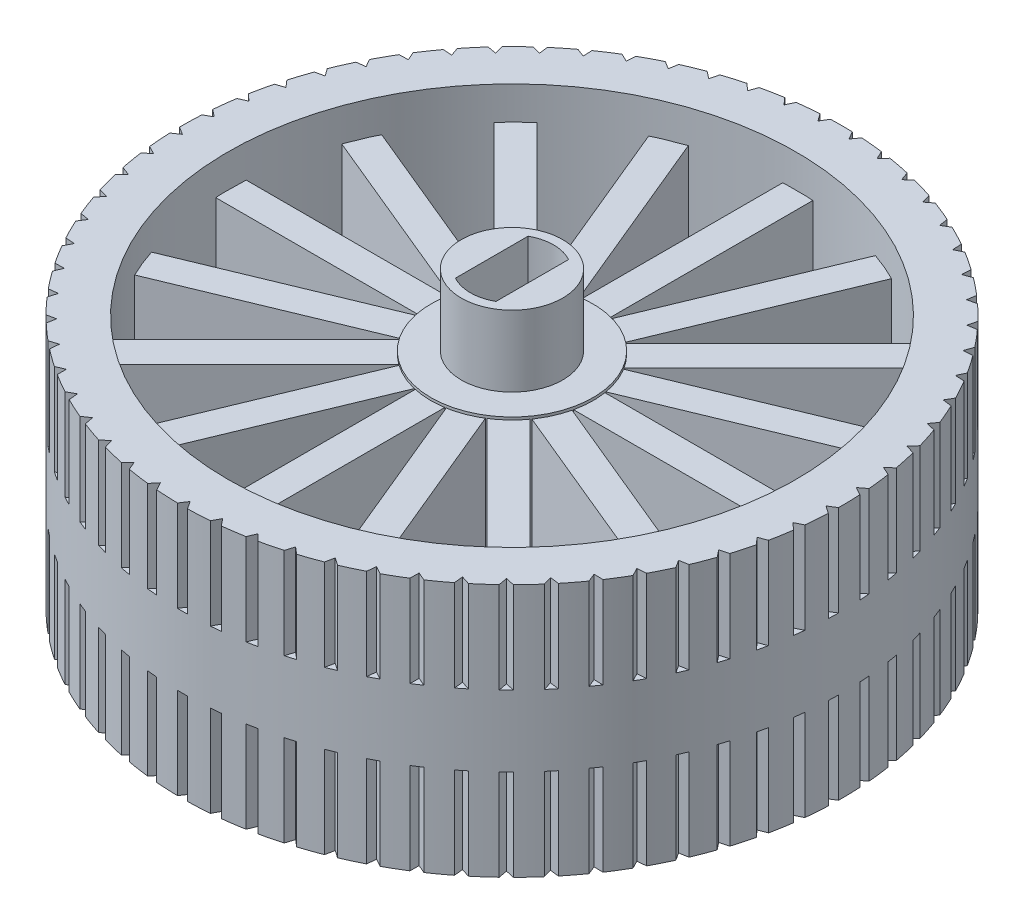
SolidWorks part; units mm, degrees
ref_plane "Front Plane" through (0, 0, 0) normal (0, 0, 1) x (1, 0, 0)
ref_plane "Top Plane" through (0, 0, 0) normal (0, 1, 0) x (1, 0, 0)
ref_plane "Right Plane" through (0, 0, 0) normal (1, 0, 0) x (0, 0, -1)
sketch "Sketch1" plane through (0, 0, 0) normal (0, 1, 0) x (1, 0, 0)
  circle A0 centre (0, 0) radius 32.5
extrude "Boss-Extrude1" add sketch "Sketch1" along normal blind 2
sketch "Sketch2" plane through (0, 2, 0) normal (0, 1, 0) x (1, 0, 0)
  circle A0 centre (0, 0) radius 4
extrude "Boss-Extrude2" add sketch "Sketch2" along normal blind 2
sketch "Sketch4" plane through (0, 4, 0) normal (0, 1, 0) x (1, 0, 0)
  line L0 (0, 4) -> (0, -4) construction
  line L1 (-4, 0) -> (-1.895, 0) construction
  line L4 (1.995, -3.5819) -> (1.995, 3.5819)
  line L5 (-1.995, 3.5819) -> (-1.995, -3.5819)
  line L7 (0, 0) -> (4, 0) construction
  circle A0 centre (0, 0) radius 4 construction
  arc A4 (1.995, 3.5819) -> (-1.995, 3.5819) centre (0, 0) ccw
  arc A5 (-1.995, -3.5819) -> (1.995, -3.5819) centre (0, 0) ccw
  point P7 (0, 0)
  point P11 (0, 0)
  point P16 (1.895, 0)
extrude "Cut-Extrude1" cut sketch "Sketch4" against normal blind 28
sketch "Sketch5" plane through (0, 2, 0) normal (0, 1, 0) x (1, 0, 0)
  circle A0 centre (0, 0) radius 8
extrude "Boss-Extrude3" add sketch "Sketch5" along normal blind 2
sketch "Sketch6" plane through (0, 2, 0) normal (0, -1, 0) x (1, 0, 0)
  line L2 (-1.995, 3.5819) -> (-1.995, -3.5819)
  line L3 (1.995, -3.5819) -> (1.995, 3.5819)
  line L4 (-1.995, 3.5819) -> (-1.995, -3.5819)
  line L5 (1.995, -3.5819) -> (1.995, 3.5819)
  arc A2 (1.995, 3.5819) -> (-1.995, 3.5819) centre (0, 0) ccw
  arc A3 (-1.995, -3.5819) -> (1.995, -3.5819) centre (0, 0) ccw
  arc A4 (1.995, 3.5819) -> (-1.995, 3.5819) centre (0, 0) ccw
  arc A5 (-1.995, -3.5819) -> (1.995, -3.5819) centre (0, 0) ccw
  dimension "D1" = 0
extrude "Cut-Extrude2" cut sketch "Sketch6" against normal through all and the other way blind 18 from offset 10
sketch "Sketch7" plane through (0, 2, 0) normal (0, 1, 0) x (1, 0, 0)
  line L0 (-1.995, -3.5819) -> (-1.995, 3.5819) construction
  line L1 (1.995, 3.5819) -> (1.995, -3.5819) construction
  line L2 (-1.995, -3.5819) -> (-1.995, 3.5819)
  line L3 (1.995, 3.5819) -> (1.995, -3.5819)
  line L4 (0, -8) -> (0, 8) construction
  line L5 (0, 8) -> (0, 28) construction
  circle A0 centre (0, 0) radius 8 construction
  circle A1 centre (0, 0) radius 8
  arc A2 (1.995, 3.5819) -> (-1.995, 3.5819) centre (0, 0) ccw construction
  arc A3 (-1.995, -3.5819) -> (1.995, -3.5819) centre (0, 0) ccw construction
  arc A4 (1.995, 3.5819) -> (-1.995, 3.5819) centre (0, 0) ccw
  arc A5 (-1.995, -3.5819) -> (1.995, -3.5819) centre (0, 0) ccw
  circle A6 centre (0, 0) radius 28
  circle A7 centre (0, 0) radius 32.5 construction
  circle A8 centre (0, 0) radius 32.5
  point P11 (0, 0)
  circle M2 centre (0, 0) radius 32.5
extrude "Boss-Extrude4" add sketch "Sketch7" along normal blind 23 contours A6 M2 region at (-31.5808, 2, 0)
sketch "Sketch9" plane through (0, 4, 0) normal (0, 1, 0) x (1, 0, 0)
  line L0 (-1.995, -3.5819) -> (-1.995, 3.5819) construction
  line L1 (1.995, 3.5819) -> (1.995, -3.5819) construction
  line L2 (-1.995, -3.5819) -> (-1.995, 3.5819)
  line L3 (1.995, 3.5819) -> (1.995, -3.5819)
  arc A0 (-1.995, -3.5819) -> (1.995, -3.5819) centre (0, 0) ccw construction
  circle A1 centre (0, 0) radius 8
  circle A2 centre (0, 0) radius 8
  arc A3 (1.995, 3.5819) -> (-1.995, 3.5819) centre (0, 0) ccw construction
  arc A4 (-1.995, -3.5819) -> (1.995, -3.5819) centre (0, 0) ccw
  arc A5 (1.995, 3.5819) -> (-1.995, 3.5819) centre (0, 0) ccw
  dimension "D1" = 0
extrude "Boss-Extrude5" add sketch "Sketch9" along normal blind 25
ref_plane "Plane1" through (-6.995, 0, 0) normal (1, 0, 0) x (0, 0, -1)
sketch "Sketch12" plane through (-6.995, 0, 0) normal (1, 0, 0) x (0, 0, -1)
  line L1 (10.471, 25) -> (-8.8085, 25) construction
  line L2 (28, 25) -> (-28, 25) construction
  line L8 (-1.2654, 21.7368) -> (1.7346, 21.7368)
  line L9 (-1.2654, 21.7368) -> (-1.2654, 2)
  line L10 (-7.6854, 2) -> (7.7278, 2) construction
  line L11 (8, 2) -> (-8, 2) construction
  line L12 (-1.2654, 2) -> (1.7346, 2)
  line L13 (1.7346, 21.7368) -> (1.7346, 2)
  line L14 (-1.2654, 21.7368) -> (1.7346, 2) construction
  line L15 (-1.2654, 2) -> (1.7346, 21.7368) construction
  point P0 (0.2346, 11.8684)
  point P11 (0.2346, 11.8684)
  dimension "D1" = 3
extrude "Boss-Extrude6" add sketch "Sketch12" against normal blind 22 separate body
pattern_circular "CirPattern2" count 16 over 360 about axis through (0, 4, 0) along (0, -1, 0) of bodies 118
sketch "Sketch13" plane through (0, 2, 0) normal (0, 1, 0) x (1, 0, 0)
  circle A1 centre (0, 0) radius 28
  circle A2 centre (0, 0) radius 28
  dimension "D1" = 0
extrude "Cut-Extrude3" cut sketch "Sketch13" against normal blind 22
sketch "Sketch14" plane through (0, 0, 0) normal (0, -1, 0) x (1, 0, 0)
  line L0 (0, 28) -> (0, 32.5) construction
  line L1 (0, 31.75) -> (-0.5277, 32.5416)
  line L6 (3.6566, 32.3357) -> (2.6154, 32.4406)
  line L7 (3.0643, 31.6018) -> (3.6566, 32.3357)
  line L8 (0, 31.75) -> (0.5187, 32.5377)
  line L9 (0.5187, 32.5377) -> (-0.5277, 32.5416)
  line L10 (3.0643, 31.6018) -> (2.6154, 32.4406)
  line L11 (6.7604, 31.8318) -> (5.7342, 32.0367)
  line L12 (6.1, 31.1585) -> (6.7604, 31.8318)
  line L13 (6.1, 31.1585) -> (5.7342, 32.0367)
  line L14 (9.8011, 31.0308) -> (8.7994, 31.3338)
  line L15 (9.0788, 30.4243) -> (9.8011, 31.0308)
  line L16 (9.0788, 30.4243) -> (8.7994, 31.3338)
  line L17 (12.7502, 29.94) -> (11.7825, 30.3382)
  line L18 (11.9728, 29.406) -> (12.7502, 29.94)
  line L19 (11.9728, 29.406) -> (11.7825, 30.3382)
  line L20 (15.5803, 28.5696) -> (14.6556, 29.0594)
  line L21 (14.755, 28.1132) -> (15.5803, 28.5696)
  line L22 (14.755, 28.1132) -> (14.6556, 29.0594)
  line L23 (18.265, 26.9325) -> (17.3918, 27.5093)
  line L24 (17.3994, 26.5579) -> (18.265, 26.9325)
  line L25 (17.3994, 26.5579) -> (17.3918, 27.5093)
  line L26 (20.779, 25.044) -> (19.9656, 25.7023)
  line L27 (19.8814, 24.7547) -> (20.779, 25.044)
  line L28 (19.8814, 24.7547) -> (19.9656, 25.7023)
  line L29 (23.0991, 22.9216) -> (22.353, 23.6554)
  line L30 (22.1777, 22.7203) -> (23.0991, 22.9216)
  line L31 (22.1777, 22.7203) -> (22.353, 23.6554)
  line L32 (25.2036, 20.5852) -> (24.5318, 21.3876)
  line L33 (24.267, 20.4737) -> (25.2036, 20.5852)
  line L34 (24.267, 20.4737) -> (24.5318, 21.3876)
  line L35 (27.0727, 18.0566) -> (26.4814, 18.92)
  line L36 (26.1297, 18.0361) -> (27.0727, 18.0566)
  line L37 (26.1297, 18.0361) -> (26.4814, 18.92)
  line L38 (28.689, 15.3594) -> (28.1838, 16.2759)
  line L39 (27.7485, 15.43) -> (28.689, 15.3594)
  line L40 (27.7485, 15.43) -> (28.1838, 16.2759)
  line L41 (30.0374, 12.5188) -> (29.6231, 13.4798)
  line L42 (29.1082, 12.6798) -> (30.0374, 12.5188)
  line L43 (29.1082, 12.6798) -> (29.6231, 13.4798)
  line L44 (31.1055, 9.5614) -> (30.7858, 10.5578)
  line L45 (30.196, 9.8113) -> (31.1055, 9.5614)
  line L46 (30.196, 9.8113) -> (30.7858, 10.5578)
  line L47 (31.8831, 6.5146) -> (31.6611, 7.5373)
  line L48 (31.002, 6.8511) -> (31.8831, 6.5146)
  line L49 (31.002, 6.8511) -> (31.6611, 7.5373)
  line L50 (32.363, 3.407) -> (32.2407, 4.4463)
  line L51 (31.5185, 3.827) -> (32.363, 3.407)
  line L52 (31.5185, 3.827) -> (32.2407, 4.4463)
  line L53 (32.5407, 0.2677) -> (32.5193, 1.3139)
  line L54 (31.7407, 0.7672) -> (32.5407, 0.2677)
  line L55 (31.7407, 0.7672) -> (32.5193, 1.3139)
  line L56 (32.4146, -2.8742) -> (32.4943, -1.8308)
  line L57 (31.6666, -2.2998) -> (32.4146, -2.8742)
  line L58 (31.6666, -2.2998) -> (32.4943, -1.8308)
  line L59 (31.9859, -5.9893) -> (32.1659, -4.9584)
  line L60 (31.2968, -5.3453) -> (31.9859, -5.9893)
  line L61 (31.2968, -5.3453) -> (32.1659, -4.9584)
  line L62 (31.2585, -9.0484) -> (31.5372, -8.0397)
  line L63 (30.6348, -8.341) -> (31.2585, -9.0484)
  line L64 (30.6348, -8.341) -> (31.5372, -8.0397)
  line L65 (30.2393, -12.023) -> (30.6141, -11.046)
  line L66 (29.6868, -11.2587) -> (30.2393, -12.023)
  line L67 (29.6868, -11.2587) -> (30.6141, -11.046)
  line L68 (28.9378, -14.8854) -> (29.4051, -13.9491)
  line L69 (28.4616, -14.0713) -> (28.9378, -14.8854)
  line L70 (28.4616, -14.0713) -> (29.4051, -13.9491)
  line L71 (27.366, -17.6088) -> (27.9215, -16.722)
  line L72 (26.9706, -16.7526) -> (27.366, -17.6088)
  line L73 (26.9706, -16.7526) -> (27.9215, -16.722)
  line L74 (25.5388, -20.1678) -> (26.1772, -19.3387)
  line L75 (25.2278, -19.2774) -> (25.5388, -20.1678)
  line L76 (25.2278, -19.2774) -> (26.1772, -19.3387)
  line L77 (23.4731, -22.5385) -> (24.1886, -21.7749)
  line L78 (23.2495, -21.6223) -> (23.4731, -22.5385)
  line L79 (23.2495, -21.6223) -> (24.1886, -21.7749)
  line L80 (21.1882, -24.6988) -> (21.9741, -24.0078)
  line L81 (21.0541, -23.7652) -> (21.1882, -24.6988)
  line L82 (21.0541, -23.7652) -> (21.9741, -24.0078)
  line L83 (18.7055, -26.6284) -> (19.5544, -26.0165)
  line L84 (18.6622, -25.6863) -> (18.7055, -26.6284)
  line L85 (18.6622, -25.6863) -> (19.5544, -26.0165)
  line L86 (16.0482, -28.3095) -> (16.9522, -27.7823)
  line L87 (16.096, -27.3675) -> (16.0482, -28.3095)
  line L88 (16.096, -27.3675) -> (16.9522, -27.7823)
  line L89 (13.241, -29.7262) -> (14.1917, -29.2888)
  line L90 (13.3795, -28.7933) -> (13.241, -29.7262)
  line L91 (13.3795, -28.7933) -> (14.1917, -29.2888)
  line L92 (10.3102, -30.8653) -> (11.2986, -30.5217)
  line L93 (10.5381, -29.9502) -> (10.3102, -30.8653)
  line L94 (10.5381, -29.9502) -> (11.2986, -30.5217)
  line L95 (7.2831, -31.7163) -> (8.3001, -31.4697)
  line L96 (7.5983, -30.8274) -> (7.2831, -31.7163)
  line L97 (7.5983, -30.8274) -> (8.3001, -31.4697)
  line L98 (4.1881, -32.2712) -> (5.2241, -32.1239)
  line L99 (4.5875, -31.4168) -> (4.1881, -32.2712)
  line L100 (4.5875, -31.4168) -> (5.2241, -32.1239)
  line L101 (1.0539, -32.5247) -> (2.0993, -32.4781)
  line L102 (1.5339, -31.7129) -> (1.0539, -32.5247)
  line L103 (1.5339, -31.7129) -> (2.0993, -32.4781)
  line L104 (-2.0901, -32.4746) -> (-1.0451, -32.5291)
  line L105 (-1.5339, -31.7129) -> (-2.0901, -32.4746)
  line L106 (-1.5339, -31.7129) -> (-1.0451, -32.5291)
  line L107 (-5.2146, -32.1213) -> (-4.1797, -32.2764)
  line L108 (-4.5875, -31.4168) -> (-5.2146, -32.1213)
  line L109 (-4.5875, -31.4168) -> (-4.1797, -32.2764)
  line L110 (-8.2904, -31.4681) -> (-7.2753, -31.7223)
  line L111 (-7.5983, -30.8274) -> (-8.2904, -31.4681)
  line L112 (-7.5983, -30.8274) -> (-7.2753, -31.7223)
  line L113 (-11.2888, -30.521) -> (-10.303, -30.872)
  line L114 (-10.5381, -29.9502) -> (-11.2888, -30.521)
  line L115 (-10.5381, -29.9502) -> (-10.303, -30.872)
  line L116 (-14.1818, -29.289) -> (-13.2345, -29.7335)
  line L117 (-13.3795, -28.7933) -> (-14.1818, -29.289)
  line L118 (-13.3795, -28.7933) -> (-13.2345, -29.7335)
  line L119 (-16.9424, -27.7835) -> (-16.0424, -28.3174)
  line L120 (-16.096, -27.3675) -> (-16.9424, -27.7835)
  line L121 (-16.096, -27.3675) -> (-16.0424, -28.3174)
  line L122 (-19.5448, -26.0186) -> (-18.7005, -26.6369)
  line L123 (-18.6622, -25.6863) -> (-19.5448, -26.0186)
  line L124 (-18.6622, -25.6863) -> (-18.7005, -26.6369)
  line L125 (-21.9647, -24.0108) -> (-21.1841, -24.7077)
  line L126 (-21.0541, -23.7652) -> (-21.9647, -24.0108)
  line L127 (-21.0541, -23.7652) -> (-21.1841, -24.7077)
  line L128 (-24.1796, -21.7788) -> (-23.4698, -22.5478)
  line L129 (-23.2495, -21.6223) -> (-24.1796, -21.7788)
  line L130 (-23.2495, -21.6223) -> (-23.4698, -22.5478)
  line L131 (-26.1687, -19.3435) -> (-25.5364, -20.1774)
  line L132 (-25.2278, -19.2774) -> (-26.1687, -19.3435)
  line L133 (-25.2278, -19.2774) -> (-25.5364, -20.1774)
  line L134 (-27.9134, -16.7275) -> (-27.3646, -17.6185)
  line L135 (-26.9706, -16.7526) -> (-27.9134, -16.7275)
  line L136 (-26.9706, -16.7526) -> (-27.3646, -17.6185)
  line L137 (-29.3975, -13.9554) -> (-28.9373, -14.8952)
  line L138 (-28.4616, -14.0713) -> (-29.3975, -13.9554)
  line L139 (-28.4616, -14.0713) -> (-28.9373, -14.8952)
  line L140 (-30.6072, -11.053) -> (-30.2398, -12.0328)
  line L141 (-29.6868, -11.2587) -> (-30.6072, -11.053)
  line L142 (-29.6868, -11.2587) -> (-30.2398, -12.0328)
  line L143 (-31.5311, -8.0474) -> (-31.26, -9.0581)
  line L144 (-30.6348, -8.341) -> (-31.5311, -8.0474)
  line L145 (-30.6348, -8.341) -> (-31.26, -9.0581)
  line L146 (-32.1606, -4.9666) -> (-31.9883, -5.9988)
  line L147 (-31.2968, -5.3453) -> (-32.1606, -4.9666)
  line L148 (-31.2968, -5.3453) -> (-31.9883, -5.9988)
  line L149 (-32.4898, -1.8395) -> (-32.4179, -2.8835)
  line L150 (-31.6666, -2.2998) -> (-32.4898, -1.8395)
  line L151 (-31.6666, -2.2998) -> (-32.4179, -2.8835)
  line L152 (-32.5156, 1.3048) -> (-32.5448, 0.2587)
  line L153 (-31.7407, 0.7672) -> (-32.5156, 1.3048)
  line L154 (-31.7407, 0.7672) -> (-32.5448, 0.2587)
  line L155 (-32.2379, 4.4369) -> (-32.3679, 3.3986)
  line L156 (-31.5185, 3.827) -> (-32.2379, 4.4369)
  line L157 (-31.5185, 3.827) -> (-32.3679, 3.3986)
  line L158 (-31.6592, 7.5276) -> (-31.8888, 6.5067)
  line L159 (-31.002, 6.8511) -> (-31.6592, 7.5276)
  line L160 (-31.002, 6.8511) -> (-31.8888, 6.5067)
  line L161 (-30.7849, 10.548) -> (-31.112, 9.554)
  line L162 (-30.196, 9.8113) -> (-30.7849, 10.548)
  line L163 (-30.196, 9.8113) -> (-31.112, 9.554)
  line L164 (-29.6231, 13.47) -> (-30.0446, 12.5121)
  line L165 (-29.1082, 12.6798) -> (-29.6231, 13.47)
  line L166 (-29.1082, 12.6798) -> (-30.0446, 12.5121)
  line L167 (-28.1848, 16.2661) -> (-28.6968, 15.3535)
  line L168 (-27.7485, 15.43) -> (-28.1848, 16.2661)
  line L169 (-27.7485, 15.43) -> (-28.6968, 15.3535)
  line L170 (-26.4833, 18.9104) -> (-27.081, 18.0514)
  line L171 (-26.1297, 18.0361) -> (-26.4833, 18.9104)
  line L172 (-26.1297, 18.0361) -> (-27.081, 18.0514)
  line L173 (-24.5346, 21.3781) -> (-25.2124, 20.5808)
  line L174 (-24.267, 20.4737) -> (-24.5346, 21.3781)
  line L175 (-24.267, 20.4737) -> (-25.2124, 20.5808)
  line L176 (-22.3567, 23.6463) -> (-23.1083, 22.9181)
  line L177 (-22.1777, 22.7203) -> (-22.3567, 23.6463)
  line L178 (-22.1777, 22.7203) -> (-23.1083, 22.9181)
  line L179 (-19.9702, 25.6936) -> (-20.7885, 25.0414)
  line L180 (-19.8814, 24.7547) -> (-19.9702, 25.6936)
  line L181 (-19.8814, 24.7547) -> (-20.7885, 25.0414)
  line L182 (-17.3972, 27.5011) -> (-18.2746, 26.9309)
  line L183 (-17.3994, 26.5579) -> (-17.3972, 27.5011)
  line L184 (-17.3994, 26.5579) -> (-18.2746, 26.9309)
  line L185 (-14.6617, 29.0517) -> (-15.5901, 28.5689)
  line L186 (-14.755, 28.1132) -> (-14.6617, 29.0517)
  line L187 (-14.755, 28.1132) -> (-15.5901, 28.5689)
  line L188 (-11.7894, 30.3312) -> (-12.76, 29.9402)
  line L189 (-11.9728, 29.406) -> (-11.7894, 30.3312)
  line L190 (-11.9728, 29.406) -> (-12.76, 29.9402)
  line L191 (-8.8069, 31.3274) -> (-9.8108, 31.0319)
  line L192 (-9.0788, 30.4243) -> (-8.8069, 31.3274)
  line L193 (-9.0788, 30.4243) -> (-9.8108, 31.0319)
  line L194 (-5.7423, 32.0312) -> (-6.77, 31.834)
  line L195 (-6.1, 31.1585) -> (-5.7423, 32.0312)
  line L196 (-6.1, 31.1585) -> (-6.77, 31.834)
  line L197 (-2.624, 32.4358) -> (-3.666, 32.3387)
  line L198 (-3.0643, 31.6018) -> (-2.624, 32.4358)
  line L199 (-3.0643, 31.6018) -> (-3.666, 32.3387)
  circle A0 centre (0, 0) radius 28 construction
  point P5 (0.0186, 32.5536)
  dimension "D1" = 65
extrude "Cut-Extrude6" cut sketch "Sketch14" against normal blind 9
ref_plane "Plane2" through (0, 12.5, 0) normal (0, 1, 0) x (1, 0, 0)
mirror "Mirror1" about plane through (0, 12.5, 0) normal (0, 1, 0) of "Cut-Extrude6"
sketch "Sketch16" plane through (0, 29, 0) normal (0, 1, 0) x (1, 0, 0)
  circle A0 centre (0, 0) radius 8 construction
  circle A1 centre (0, 0) radius 8
  circle A2 centre (0, 0) radius 5
extrude "Cut-Extrude7" cut sketch "Sketch16" against normal blind 7
